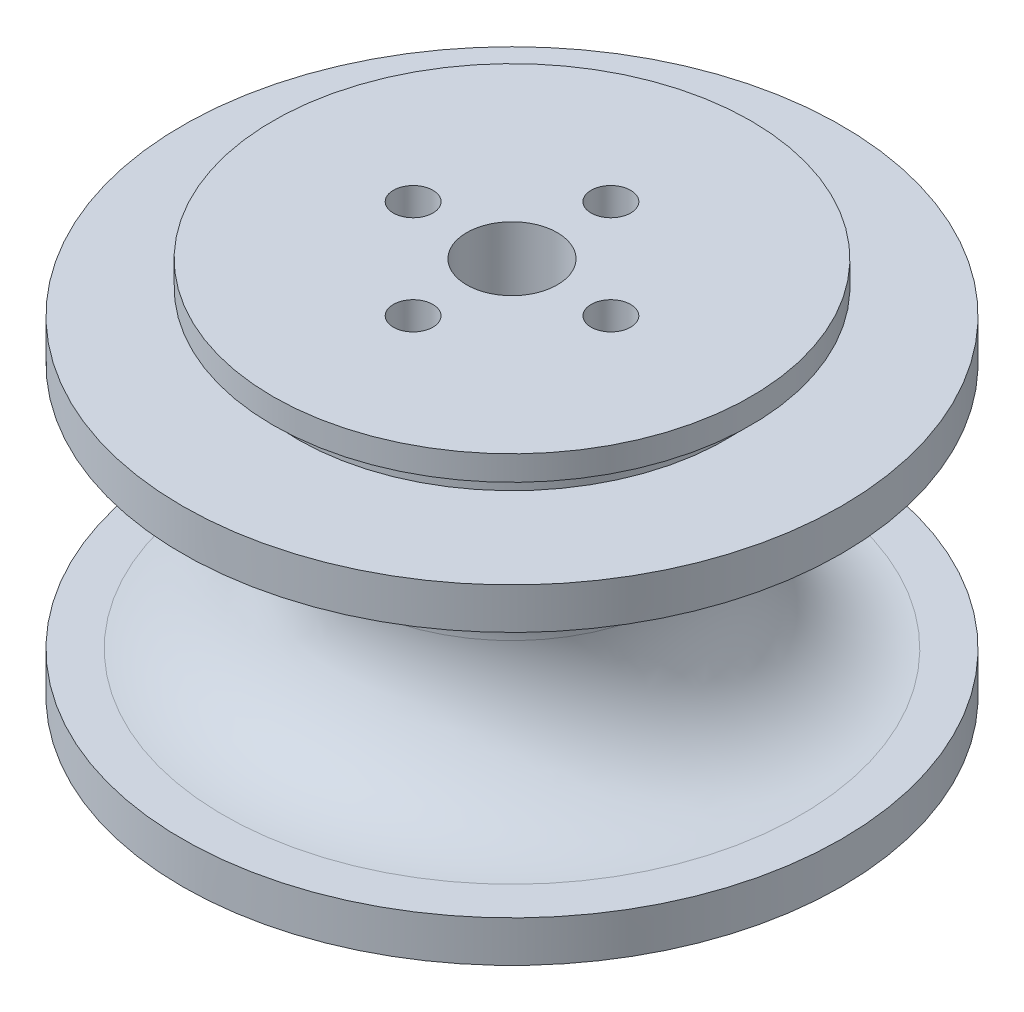
SolidWorks part; units mm, degrees
ref_plane "前视基准面" through (0, 0, 0) normal (0, 0, 1) x (1, 0, 0)
ref_plane "上视基准面" through (0, 0, 0) normal (0, 1, 0) x (1, 0, 0)
ref_plane "右视基准面" through (0, 0, 0) normal (1, 0, 0) x (0, 0, -1)
other "Configuration Table"
sketch "草图1" plane through (0, 0, 0) normal (0, 1, 0) x (1, 0, 0)
  circle A0 centre (0, 0) radius 40
  dimension "D1" = 80
extrude "凸台-拉伸1" add sketch "草图1" along normal blind 40
sketch "草图2" plane through (0, 40, 0) normal (0, 1, 0) x (1, 0, 0)
  circle A0 centre (0, 0) radius 26
  dimension "D1" = 52
extrude "凸台-拉伸2" add sketch "草图2" along normal blind 3
sketch "草图3" plane through (0, 43, 0) normal (0, 1, 0) x (1, 0, 0)
  circle A0 centre (0, 0) radius 29
  dimension "D1" = 58
extrude "凸台-拉伸3" add sketch "草图3" along normal blind 3
fillet "圆角1" radius 1 1 edges at (0, 43, 26)
sketch "草图4" plane through (0, 0, 0) normal (0, -1, 0) x (1, 0, 0)
  circle A0 centre (0, 0) radius 26
  dimension "D1" = 52
extrude "凸台-拉伸4" add sketch "草图4" along normal blind 3
sketch "草图5" plane through (0, -3, 0) normal (0, -1, 0) x (1, 0, 0)
  circle A0 centre (0, 0) radius 28
  dimension "D1" = 56
extrude "凸台-拉伸5" add sketch "草图5" along normal blind 3
fillet "圆角2" radius 1 1 edges at (0, -3, -26)
sketch "草图6" plane through (0, 0, 0) normal (0, 0, 1) x (1, 0, 0)
  line L0 (0, -960) -> (0, 49040) construction
  line L1 (40, 40) -> (-40, 40) construction
  line L5 (-40, 35) -> (-20, 35)
  line L6 (-20, 5) -> (-20, 35)
  line L7 (-40, 5) -> (-20, 5)
  line L8 (-40, 35) -> (-40, 5)
  point P5 (0, 40)
  dimension "D2" = 20
revolve "切除-旋转1" cut sketch "草图6" angle 360 about L0
fillet "圆角5" radius 15 2 edges at (20, 5, 0) (20, 35, 0)
sketch "草图7" plane through (0, -6, 0) normal (0, -1, 0) x (1, 0, 0)
  circle A0 centre (0, 0) radius 5.5
  dimension "D1" = 11
extrude "切除-拉伸1" cut sketch "草图7" against normal through all
sketch "草图8" plane through (0, -6, 0) normal (0, -1, 0) x (1, 0, 0)
  circle A0 centre (0, 0) radius 12
  circle A1 centre (0, 12) radius 2.4
  circle A2 centre (12, 0) radius 2.4
  circle A3 centre (0, -12) radius 2.4
  circle A4 centre (-12, 0) radius 2.4
  point P14 (0, 0)
  dimension "D1" = 24
  dimension "D2" = 4.8
  dimension "D3" = 4
extrude "切除-拉伸2" cut sketch "草图8" against normal through all contours A1 | A4 | A3 | A2
